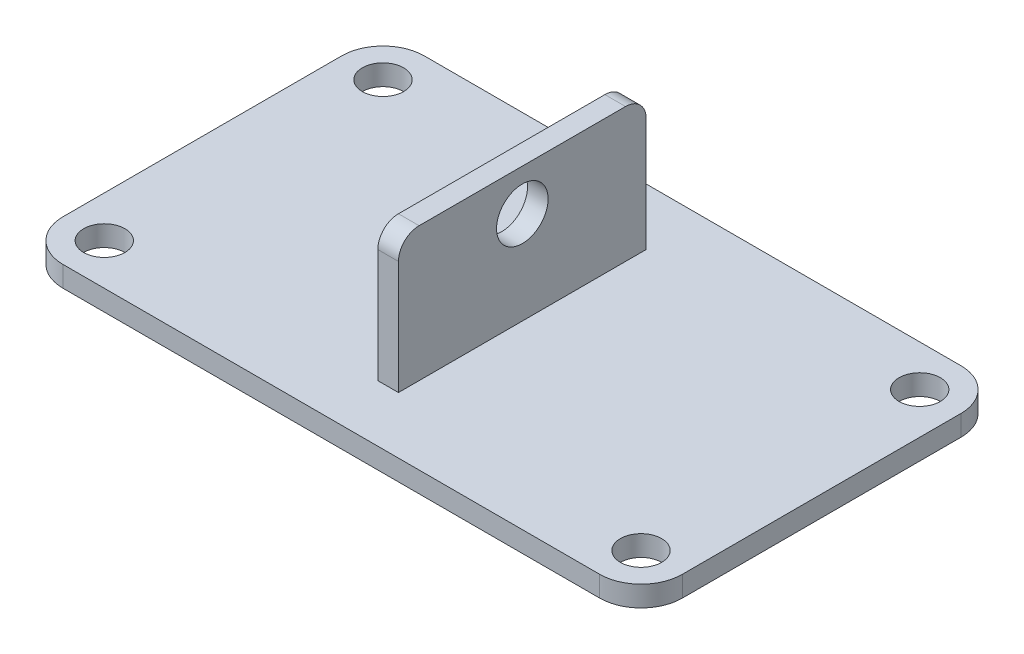
SolidWorks part; units mm, degrees
ref_plane "Front Plane" through (0, 0, 0) normal (0, 0, 1) x (1, 0, 0)
ref_plane "Top Plane" through (0, 0, 0) normal (0, 1, 0) x (1, 0, 0)
ref_plane "Right Plane" through (0, 0, 0) normal (1, 0, 0) x (0, 0, -1)
sketch "Sketch2" plane through (0, 0, 0) normal (0, 1, 0) x (1, 0, 0)
  line L0 (0, 129.0501) -> (0, -129.7351) construction
  line L1 (-130, -87.5) -> (130, -87.5)
  line L2 (-150, -67.5) -> (-150, 67.5)
  line L3 (-130, 87.5) -> (130, 87.5)
  line L4 (150, -67.5) -> (150, 67.5)
  line L5 (163.5798, 0) -> (-203.5341, 0) construction
  line L7 (-5, -60) -> (5, -60)
  line L8 (-5, -60) -> (-5, 60)
  line L9 (-5, 60) -> (5, 60)
  line L10 (5, -60) -> (5, 60)
  line L11 (-5, -60) -> (5, 60) construction
  line L12 (-5, 60) -> (5, -60) construction
  arc A0 (130, 87.5) -> (150, 67.5) centre (130, 67.5) cw
  circle A1 centre (130, 67.5) radius 10
  arc A2 (-130, 87.5) -> (-150, 67.5) centre (-130, 67.5) ccw
  circle A3 centre (-130, 67.5) radius 10
  arc A4 (130, -87.5) -> (150, -67.5) centre (130, -67.5) ccw
  circle A5 centre (130, -67.5) radius 10
  arc A6 (-130, -87.5) -> (-150, -67.5) centre (-130, -67.5) cw
  circle A7 centre (-130, -67.5) radius 10
  point P0 (0, 0)
  point P2 (0, 0)
  point P8 (150, 87.5)
  point P28 (5, -60)
  dimension "D3" = 20
  dimension "D1" = 10
  dimension "D2" = 120
extrude "Boss-Extrude1" add sketch "Sketch2" along normal blind 10
extrude "Boss-Extrude2" add sketch "Sketch2<3>" along normal blind 75 contours L7 L10 L9 L8 region at (0, 0, 0)
sketch "Sketch2<3>" plane through (0, 0, 0) normal (0, 1, 0) x (1, 0, 0) same geometry as "Sketch2"
fillet "Fillet1" radius 10 2 edges at (0, 75, -60) (0, 75, 60)
sketch "Sketch3" plane through (5, 0, 0) normal (1, 0, 0) x (0, 0, -1)
  circle A0 centre (0, 55) radius 12.5
  dimension "D1" = 55
extrude "Cut-Extrude1" cut sketch "Sketch3" against normal blind 75
